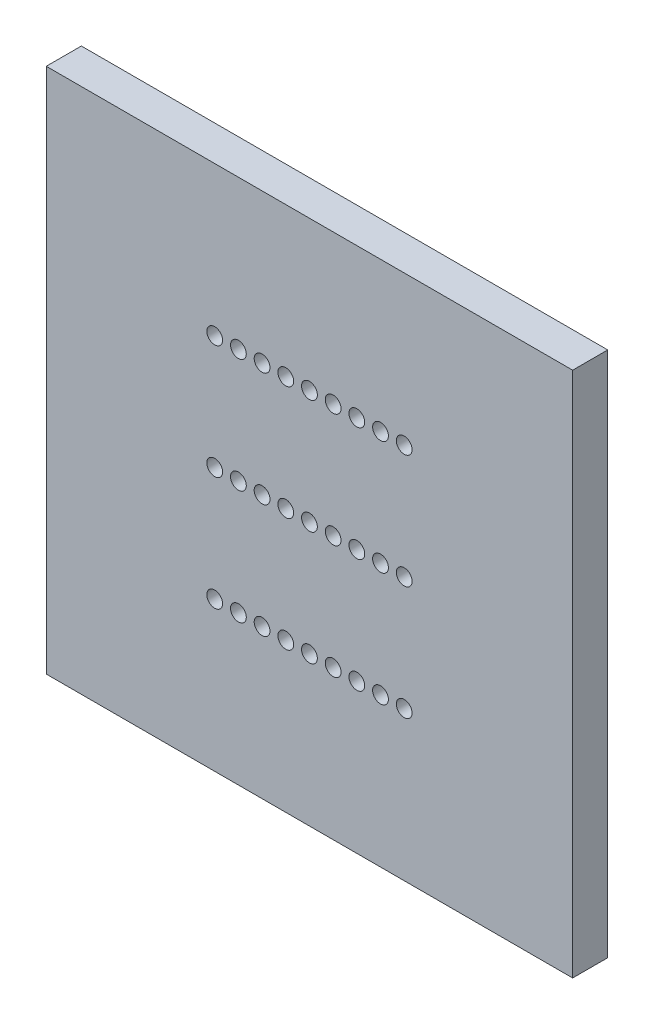
SolidWorks part; units mm, degrees
ref_plane "Plan de face" through (0, 0, 0) normal (0, 0, 1) x (1, 0, 0)
ref_plane "Plan de dessus" through (0, 0, 0) normal (0, 1, 0) x (1, 0, 0)
ref_plane "Plan de droite" through (0, 0, 0) normal (1, 0, 0) x (0, 0, -1)
sketch "Esquisse2" plane through (0, 0, 0) normal (0, 0, 1) x (1, 0, 0)
  line L1 (-15, -15) -> (15, -15)
  line L2 (-15, -15) -> (-15, 15)
  line L3 (-15, 15) -> (15, 15)
  line L4 (15, -15) -> (15, 15)
  line L5 (-15, -15) -> (15, 15) construction
  line L6 (-15, 15) -> (15, -15) construction
  point P0 (0, 0)
extrude "Boss.-Extru.1" add sketch "Esquisse2" along normal blind 2
sketch "Esquisse3" plane through (0, 0, 2) normal (0, 0, 1) x (1, 0, 0)
  circle A0 centre (-5.4, -6.5) radius 0.45
  circle A1 centre (-5.4, 0) radius 0.45
  circle A2 centre (-5.4, 6.5) radius 0.45
  circle A3 centre (-4.05, -6.5) radius 0.45
  circle A4 centre (-4.05, 0) radius 0.45
  circle A5 centre (-4.05, 6.5) radius 0.45
  circle A6 centre (-2.7, -6.5) radius 0.45
  circle A7 centre (-2.7, 0) radius 0.45
  circle A8 centre (-2.7, 6.5) radius 0.45
  circle A9 centre (-1.35, -6.5) radius 0.45
  circle A10 centre (-1.35, 0) radius 0.45
  circle A11 centre (-1.35, 6.5) radius 0.45
  circle A12 centre (0, -6.5) radius 0.45
  circle A13 centre (0, 0) radius 0.45
  circle A14 centre (0, 6.5) radius 0.45
  circle A15 centre (1.35, -6.5) radius 0.45
  circle A16 centre (1.35, 0) radius 0.45
  circle A17 centre (1.35, 6.5) radius 0.45
  circle A18 centre (2.7, -6.5) radius 0.45
  circle A19 centre (2.7, 0) radius 0.45
  circle A20 centre (2.7, 6.5) radius 0.45
  circle A21 centre (4.05, -6.5) radius 0.45
  circle A22 centre (4.05, 0) radius 0.45
  circle A23 centre (4.05, 6.5) radius 0.45
  circle A24 centre (5.4, -6.5) radius 0.45
  circle A25 centre (5.4, 0) radius 0.45
  circle A26 centre (5.4, 6.5) radius 0.45
extrude "Enlèv. mat.-Extru.1" cut sketch "Esquisse3" against normal blind 10
